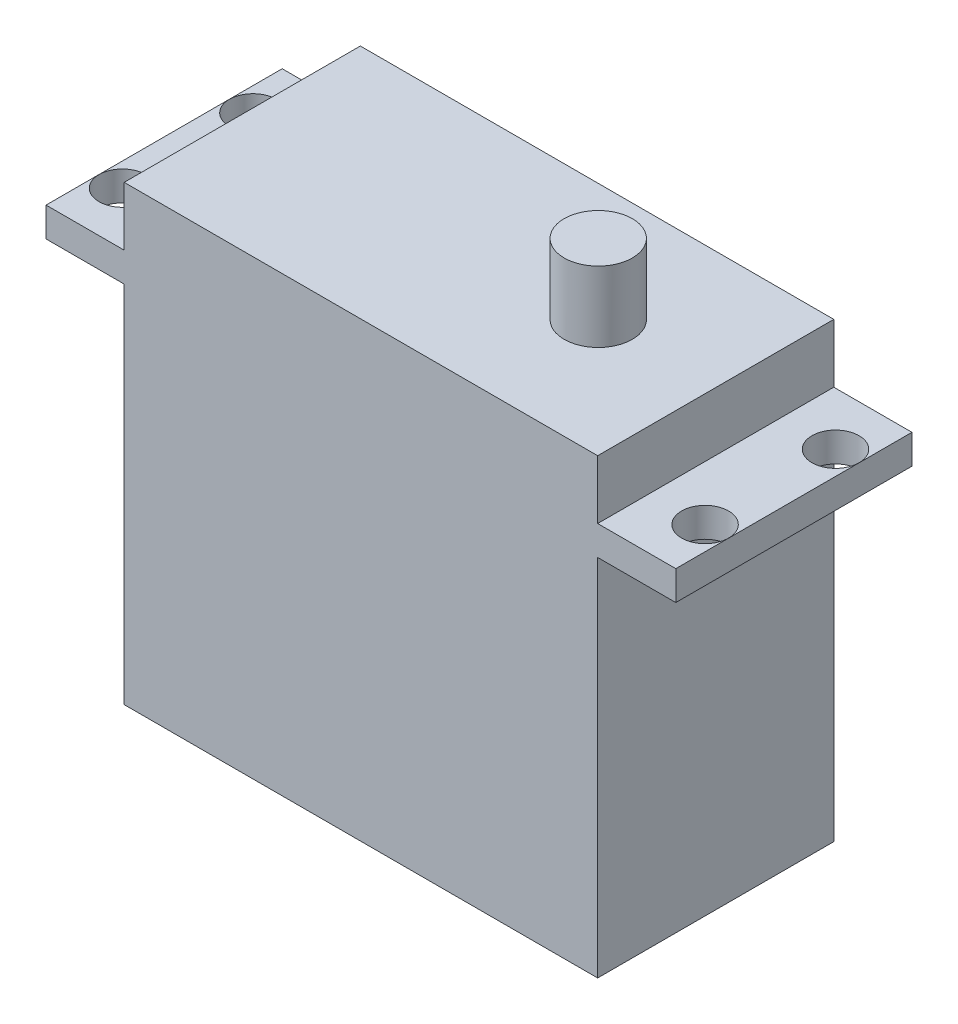
SolidWorks part; units mm, degrees
ref_plane "Front Plane" through (0, 0, 0) normal (0, 0, 1) x (1, 0, 0)
ref_plane "Top Plane" through (0, 0, 0) normal (0, 1, 0) x (1, 0, 0)
ref_plane "Right Plane" through (0, 0, 0) normal (1, 0, 0) x (0, 0, -1)
sketch "Sketch1" plane through (0, 0, 0) normal (0, 1, 0) x (1, 0, 0)
  line L1 (-20.15, -10.05) -> (20.15, -10.05)
  line L2 (-20.15, -10.05) -> (-20.15, 10.05)
  line L3 (-20.15, 10.05) -> (20.15, 10.05)
  line L4 (20.15, -10.05) -> (20.15, 10.05)
  line L5 (-20.15, -10.05) -> (20.15, 10.05) construction
  line L6 (-20.15, 10.05) -> (20.15, -10.05) construction
  point P0 (0, 0)
  dimension "D1" = 20.1
  dimension "D2" = 40.3
extrude "Boss-Extrude1" add sketch "Sketch1" along normal blind 38.5
sketch "Sketch2" plane through (0, 38.5, 0) normal (0, 1, 0) x (1, 0, 0)
  line L0 (20.15, 0) -> (10.15, 0) construction
  line L1 (20.15, -10.05) -> (20.15, 10.05) construction
  circle A0 centre (10.15, 0) radius 2.9
  dimension "D2" = 5.8
  dimension "D1" = 10
extrude "Boss-Extrude2" add sketch "Sketch2" along normal blind 6
sketch "Sketch3" plane through (0, 38.5, 0) normal (0, 1, 0) x (1, 0, 0)
  line L0 (-26.8, 0) -> (26.8, 0) construction
  line L1 (-20.15, 10.05) -> (-26.8, 10.05)
  line L2 (-20.15, -10.05) -> (-26.8, -10.05)
  line L3 (-26.8, -10.05) -> (-26.8, 10.05)
  line L4 (20.15, 10.05) -> (26.8, 10.05)
  line L5 (26.8, 10.05) -> (26.8, -10.05)
  line L6 (26.8, -10.05) -> (20.15, -10.05)
  line L7 (-20.15, 10.05) -> (-20.15, -10.05)
  line L8 (20.15, 10.05) -> (20.15, -10.05)
  line L9 (-26.8, 3.75) -> (-26.8, -3.75)
  line L10 (0, -10.05) -> (0, 10.05) construction
  line L11 (-20.15, -10.05) -> (20.15, -10.05) construction
  line L12 (20.15, 10.05) -> (-20.15, 10.05) construction
  circle A0 centre (-24.7944, 5.55) radius 2
  circle A1 centre (-24.7944, -5.55) radius 2
  circle A2 centre (24.7944, -5.55) radius 2
  circle A3 centre (24.7944, 5.55) radius 2
  point P4 (0, 0)
  point P20 (-26.8, 0)
  line M4 (20.15, -10.05) -> (20.15, 10.05)
  line M6 (-20.15, 10.05) -> (-20.15, -10.05)
  dimension "D4" = 4
  dimension "D5" = 4.5
  dimension "D1" = 53.6
  dimension "D2" = 6.65
extrude "Boss-Extrude3" add sketch "Sketch3" against normal blind 2.5 from offset 5 contours L3 L2 L1 A0 A1 M6 | L6 L5 L4 A2 A3 M4 region at (-23.1695, 38.5, 0) region at (23.1695, 38.5, 0) offset against normal yes
